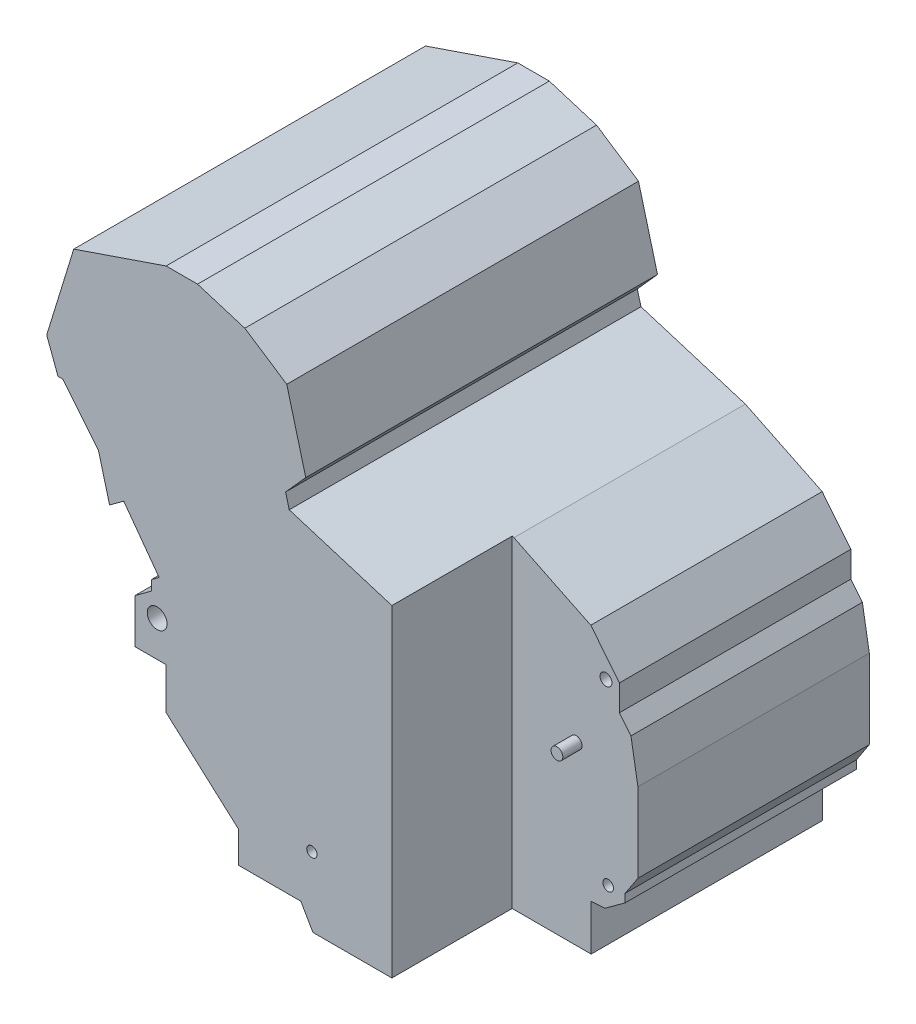
SolidWorks part; units mm, degrees
ref_plane "Front Plane" through (0, 0, 0) normal (0, 0, 1) x (1, 0, 0)
ref_plane "Top Plane" through (0, 0, 0) normal (0, 1, 0) x (1, 0, 0)
ref_plane "Right Plane" through (0, 0, 0) normal (1, 0, 0) x (0, 0, -1)
sketch "Sketch1" plane through (35.4966, -5.137, 0) normal (0, 0, 1) x (1, 0, 0)
  line L0 (105.9127, 212.0891) -> (129.7931, 202.7919) construction
  line L1 (298.0513, -7.0403) -> (468.6681, -7.0403)
  line L2 (468.6681, -7.0403) -> (468.6681, 42.2394)
  line L3 (298.0513, -7.0403) -> (284.9999, 15.6075)
  line L4 (284.9999, 15.6075) -> (217.5018, 15.6075)
  line L5 (217.5018, 15.6075) -> (217.5018, 49.5861)
  line L6 (217.5018, 49.5861) -> (139.4428, 119.38)
  line L7 (139.4428, 119.38) -> (139.4428, 164.1447)
  line L8 (139.4428, 164.1447) -> (105.9127, 164.1447)
  line L9 (105.9127, 164.1447) -> (105.9127, 212.0891)
  line L10 (105.9127, 212.0891) -> (123.793, 225.1611)
  line L11 (123.793, 225.1611) -> (123.793, 236.0135)
  line L12 (123.793, 236.0135) -> (131.9204, 241.9553)
  line L13 (131.9204, 241.9553) -> (93.704, 294.2287)
  line L14 (93.704, 294.2287) -> (78.403, 283.0424)
  line L15 (78.403, 283.0424) -> (66.4689, 327.8212)
  line L16 (22.6747, 375.5398) -> (10.4607, 408.0912)
  line L17 (66.4689, 327.8212) -> (28.0229, 375.5398)
  line L18 (28.0229, 375.5398) -> (22.6747, 375.5398)
  line L19 (10.4607, 408.0912) -> (39.6926, 503.0865)
  line L20 (39.6926, 503.0865) -> (139.4428, 537.1589)
  line L21 (139.4428, 537.1589) -> (173.4449, 537.1589)
  line L22 (173.4449, 537.1589) -> (224.4833, 521.4534)
  line L23 (224.4833, 521.4534) -> (269.8091, 491.6488)
  line L24 (269.8091, 491.6488) -> (290.3368, 414.6254)
  line L25 (290.3368, 414.6254) -> (268.5529, 390.2617)
  line L26 (268.5529, 390.2617) -> (272.4764, 375.5398)
  line L27 (272.4764, 375.5398) -> (385.2118, 340.849)
  line L28 (385.2118, 340.849) -> (468.24, 300.4646)
  line L29 (468.24, 300.4646) -> (499.222, 262.0102)
  line L30 (499.222, 262.0102) -> (499.222, 234.0511)
  line L31 (499.222, 234.0511) -> (511.6504, 218.6251)
  line L32 (511.6504, 218.6251) -> (519.1533, 174.7609)
  line L33 (519.1533, 174.7609) -> (519.1533, 89.1554)
  line L34 (519.1533, 89.1554) -> (505.4362, 68.2949)
  line L35 (505.4362, 68.2949) -> (505.4362, 59.3059)
  line L36 (505.4362, 59.3059) -> (483.731, 43.4375)
  line L37 (483.731, 43.4375) -> (468.6681, 42.2394)
  line L38 (284.9999, 15.6075) -> (296.9413, 67.9155) construction
  line L39 (468.6681, 42.2394) -> (487.0386, 66.4385) construction
  line L40 (499.222, 262.0102) -> (484.6624, 257.9155)
  circle A0 centre (129.7931, 202.7919) radius 10.6899
  circle A1 centre (296.9413, 67.9155) radius 5.5517
  circle A2 centre (487.0386, 66.4385) radius 5.7409
  circle A3 centre (484.6624, 257.9155) radius 6.4147
  dimension "D52" = 21.3798
  dimension "D56" = 11.1034
  dimension "D58" = 11.4819
  dimension "D61" = 12.8293
  dimension "D1" = 170.6168
  dimension "D2" = 49.2797
  dimension "D3" = 119.954
  dimension "D4" = 67.4981
  dimension "D5" = 33.9786
  dimension "D6" = 69.7939
  dimension "D7" = 138.2
  dimension "D8" = 22.6478
  dimension "D9" = 44.7646
  dimension "D10" = 33.5301
  dimension "D11" = 47.9444
  dimension "D12" = 13.0721
  dimension "D13" = 126.17
  dimension "D14" = 10.8524
  dimension "D15" = 64.7534
  dimension "D16" = 10.0677
  dimension "D17" = 15.301
  dimension "D18" = 44.7788
  dimension "D19" = 68.753
  dimension "D20" = 61.2793
  dimension "D21" = 203.935
  dimension "D22" = 110.567
  dimension "D23" = 32.5514
  dimension "D24" = 5.3482
  dimension "D25" = 99.3912
  dimension "D26" = 142.329
  dimension "D27" = 125.963
  dimension "D28" = 105.4089
  dimension "D29" = 34.0021
  dimension "D30" = 51.0384
  dimension "D31" = 196.223
  dimension "D32" = 54.2471
  dimension "D33" = 24.3637
  dimension "D34" = 14.7219
  dimension "D35" = 112.7353
  dimension "D36" = 123.276
  dimension "D37" = 77.0234
  dimension "D38" = 188.834
  dimension "D39" = 92.3287
  dimension "D40" = 49.3824
  dimension "D41" = 19.8098
  dimension "D42" = 141.142
  dimension "D43" = 150.849
  dimension "D44" = 43.8642
  dimension "D45" = 85.6055
  dimension "D46" = 24.9664
  dimension "D47" = 146.673
  dimension "D48" = 8.989
  dimension "D49" = 26.8872
  dimension "D50" = 15.0629
  dimension "D51" = 85.452
  dimension "D53" = 57.442
  dimension "D54" = 23.8804
  dimension "D55" = 52.308
  dimension "D57" = 102.86
  dimension "D59" = 30.3822
  dimension "D60" = 48.249
  dimension "D62" = 14.5595
  dimension "D63" = 74.292
extrude "Boss-Extrude1" add sketch "Sketch1" along normal blind 190 and the other way blind 190 contours A3 L29 L28 L27 L26 L25 L24 L23 L22 L21 L20 L19 L16 L18 L17 L15 L14 L13 L12 L11 L10 L9 L8 L7 L6 L5 L4 L3 L1 L2 L37 L36 L35 L34 L33 L32 L31 L30 A2 A1 A0 region at (306.7635, 244.1777, 0)
sketch "Sketch2" plane through (0, 0, 190) normal (0, 0, 1) x (1, 0, 0)
  line L0 (418.8563, -12.1773) -> (418.8563, 350.2741)
  line L1 (333.5479, -12.1773) -> (504.1647, -12.1773) construction
  line L2 (418.8563, 350.2741) -> (582.6587, 350.2741)
  line L3 (582.6587, 350.2741) -> (582.6587, -17.8458)
  line L4 (582.6587, -17.8458) -> (418.8563, -17.8458)
  line L5 (418.8563, -17.8458) -> (418.8563, -12.1773)
extrude "Cut-Extrude1" cut sketch "Sketch2" against normal blind 130
sketch "Sketch3" plane through (0, 0, 60) normal (0, 0, 1) x (1, 0, 0)
  circle A0 centre (488.0224, 177.8032) radius 6.35
  dimension "D1" = 12.7
extrude "Boss-Extrude2" add sketch "Sketch3" along normal blind 20.8423
equation "\"frontSprocket_keyLength\"= 20.842314mm"
equation "\"D1@Boss-Extrude2\"=\"frontSprocket_keyLength\""
